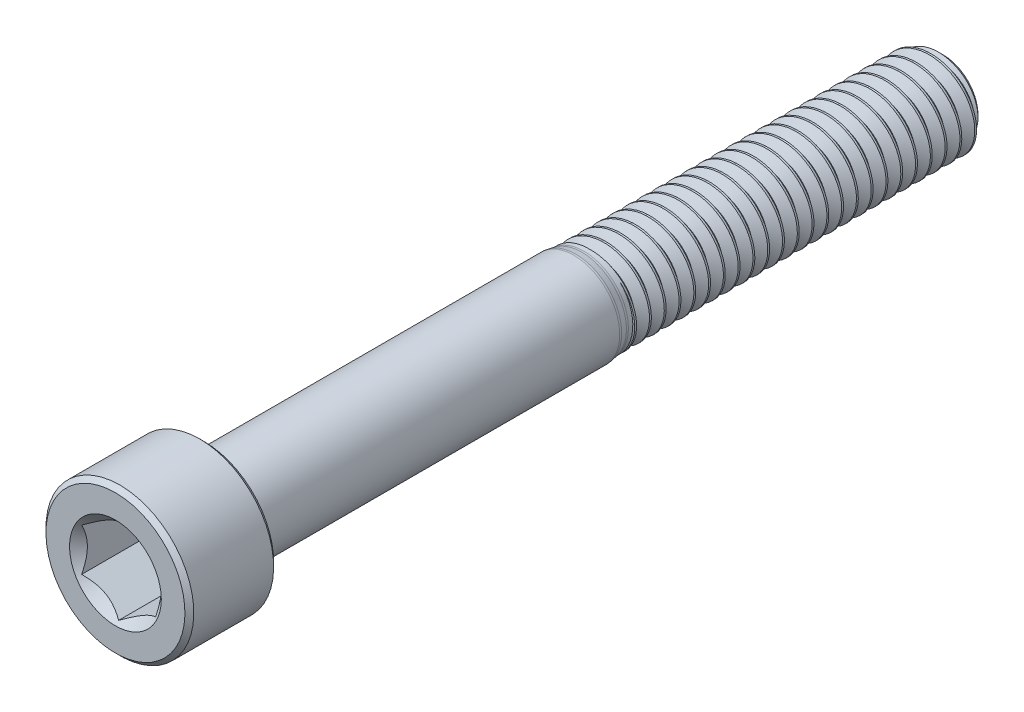
SolidWorks part; units mm, degrees
ref_plane "Front Plane" through (0, 0, 0) normal (0, 0, 1) x (1, 0, 0)
ref_plane "Top Plane" through (0, 0, 0) normal (0, 1, 0) x (1, 0, 0)
ref_plane "Right Plane" through (0, 0, 0) normal (1, 0, 0) x (0, 0, -1)
sketch "Sketch1" plane through (0, 0, 0) normal (1, 0, 0) x (0, 0, -1)
  line L0 (-28, 0) -> (28, 0) construction
  line L1 (28, 0) -> (28, 2.3505) construction
  line L2 (28, 2.3505) -> (27.3505, 3) construction
  line L3 (27.3505, 3) -> (27.25, 3) construction
  line L4 (27.25, 3) -> (-22, 3) construction
  line L5 (-22, 3) -> (-22, 5) construction
  line L6 (-22, 5) -> (-28, 5) construction
  line L7 (-28, 5) -> (-28, 0) construction
  line L8 (28, 2.3505) -> (28, 3) construction
  line L9 (27.9375, 3.1083) -> (28.4375, 2.2422) construction
  line L10 (28.4375, 2.2422) -> (28.9375, 3.1083) construction
  line L11 (28.9375, 3.1083) -> (27.9375, 3.1083) construction
  line L12 (28.4375, 3.1083) -> (28.4375, 3) construction
  line L13 (28.4375, 2.2422) -> (28.4375, 2.3505) construction
  line L14 (28.375, 2.3505) -> (28.5, 2.3505) construction
  line L15 (28, 3) -> (28.875, 3) construction
  line L16 (27.9688, 3.0541) -> (28.9062, 3.0541) construction
  line L17 (28, 0) -> (28, -3) construction
  line L18 (-22.3, 5) -> (-22, 4.7) construction
  line L19 (-27.7, 5) -> (-28, 4.7) construction
  line L20 (-22, 3) -> (-22, 0) construction
  line L21 (-22, 1.5) -> (-5.3333, 1.5) construction
  line L22 (-5.3333, 1.5) -> (11.3333, 1.5) construction
  line L23 (11.3333, 1.5) -> (28, 1.5) construction
  line L24 (-5.3333, 1.5) -> (-5.3333, 3) construction
  line L25 (-5.3333, 3) -> (-5.3333, 5) construction
  line L26 (11.3333, 1.5) -> (11.3333, 5) construction
  point P0 (-28, 2.5)
  point P3 (25.5, 3)
  point P4 (0, 0)
  point P18 (11.3333, 3)
  point P22 (28.4375, 2.3505)
  point P24 (27.25, 3)
  point P25 (28.4375, 3)
  point P28 (28.4375, 3.0541)
  point P29 (25.5, -3)
  point P30 (-5.3333, 3)
  point P31 (-25, 5)
  point P37 (-23.05, 5)
  point P38 (-27.55, 5)
  point P45 (-5.3333, 1.5)
  point P46 (11.3333, 1.5)
  point P49 (4, 3)
  dimension "D1" = 45
  dimension "D2" = 0.125
  dimension "D7" = 0.3
  dimension "D8" = 0.3
  dimension "D9" = 0.3
  dimension "D10" = 0.15
  dimension "D11" = 0.75
  dimension "Drive Size" = 5
  dimension "Head Diameter" = 10
  dimension "Head Height" = 6
  dimension "Thread Pitch" = 1
  dimension "Thread Dia" = 6
  dimension "Length" = 50
  dimension "D12" = 0.75
  dimension "D4" = 2.5
  dimension "Minimum Thread Length" = 24
  dimension "D3" = 26
sketch "Sketch2" plane through (0, 0, 0) normal (1, 0, 0) x (0, 0, -1)
  line L0 (-28, 0) -> (-28, 4.7)
  line L1 (-27.7, 5) -> (-22.3, 5)
  line L2 (-22, 4.7) -> (-22, 3.4083)
  line L4 (27.3505, 3) -> (28, 2.3505)
  line L5 (28, 2.3505) -> (28, 0)
  line L6 (-22, 5) -> (-28, 5) construction
  line L7 (28, 0) -> (-28, 0)
  line L8 (-27.7, 5) -> (-28, 4.7) construction
  line L10 (-27.7, 5) -> (-28, 4.7)
  line L14 (-22.3, 5) -> (-22, 4.7) construction
  line L16 (-22.3, 5) -> (-22, 4.7)
  line L17 (-22, 3) -> (-22, 5) construction
  line L18 (-21.7, 3.1083) -> (3.0069, 3.1083)
  line L19 (3.6989, 3) -> (27.3505, 3)
  line L20 (27.25, 3) -> (-22, 3) construction
  line L21 (3.1532, 3.0938) -> (3.5526, 3.0144)
  line L22 (28.9375, 3.1083) -> (27.9375, 3.1083) construction
  arc A1 (-22, 3.4083) -> (-21.7, 3.1083) centre (-21.7, 3.4083) ccw
  arc A2 (3.0069, 3.1083) -> (3.1532, 3.0938) centre (3.0069, 2.3583) cw
  arc A3 (3.5526, 3.0144) -> (3.6989, 3) centre (3.6989, 3.75) ccw
  point P39 (3.625, 3)
  dimension "D3" = 0.3
  dimension "D6" = 0.75
  dimension "D4" = 11.25
  dimension "D5" = 0.375
revolve "Revolve1" add sketch "Sketch2" angle 360 about L7
sketch "Sketch3" plane through (0, 0, 28) normal (0, 0, 1) x (1, 0, 0)
  line L1 (2.5, -1.4434) -> (2.5, 1.4434)
  line L2 (2.5, 1.4434) -> (0, 2.8868)
  line L3 (0, 2.8868) -> (-2.5, 1.4434)
  line L4 (-2.5, 1.4434) -> (-2.5, -1.4434)
  line L5 (-2.5, -1.4434) -> (0, -2.8868)
  line L6 (0, -2.8868) -> (2.5, -1.4434)
  circle A0 centre (0, 0) radius 2.5 construction
  circle A1 centre (0, 0) radius 5 construction
  circle A2 centre (0, 0) radius 5 construction
  circle A3 centre (0, 0) radius 2.8868 construction
  dimension "D1" = 5.7735
extrude "Cut-Extrude1" cut sketch "Sketch3" against normal offset from surface (5 mm away) 1 up to face at (0, 4.7, 22)
sketch "Sketch4" plane through (0, 0, 28) normal (0, 0, 1) x (1, 0, 0)
  circle A0 centre (0, 0) radius 3.1033
  dimension "D1" = 6.2065
extrude "Cut-Extrude2" cut sketch "Sketch4" against normal up to vertex (3 mm away) draft 45 up to point (0, 5, 25)
sketch "Sketch11" plane through (0, 0, 0) normal (1, 0, 0) x (0, 0, -1)
  line L0 (-28, 0) -> (28, 0) construction
  line L1 (-28, 0) -> (28, 0) construction
  line L2 (-18.75, 0) -> (-18.75, 3) construction
  line L3 (27.25, 3) -> (-22, 3) construction
  line L4 (-0.2431, 0) -> (-0.2431, 3) construction
  point P2 (-18.75, 0)
  point P3 (-0.2431, 0)
  dimension "D1" = 3.25
  dimension "D2" = 3.25
sketch "Sketch6" plane through (0, 0, -28) normal (0, 0, -1) x (-1, 0, 0)
  circle A0 centre (0, 0) radius 3
curve "Helix/Spiral1" pitch 1 height 25 radius 3 centre (0, 0, -28) axis (0, 0, 1) start towards (0, 1, 0)
sketch "Sketch10" plane through (0, 0, 0) normal (1, 0, 0) x (0, 0, -1)
  line L0 (4, -3) -> (4, 3)
  line L2 (-28, 0) -> (28, 0) construction
  point P3 (4, 0)
split "Split1" trim tools "Sketch10" bodies to split 106 resulting bodies 114 115
sketch "Sketch7" plane through (0, 0, 0) normal (1, 0, 0) x (0, 0, -1)
  line L0 (27.9688, 3.0541) -> (28.9062, 3.0541)
  line L1 (28.9062, 3.0541) -> (28.5, 2.3505)
  line L2 (28.5, 2.3505) -> (28.375, 2.3505)
  line L3 (28.375, 2.3505) -> (27.9688, 3.0541)
sweep "Cut-Sweep1" cut profiles "Sketch7" path "Helix/Spiral1" align with end faces yes
sketch "Sketch8" plane through (0, 0, 0) normal (1, 0, 0) x (0, 0, -1)
  line L0 (-22, 0) -> (-22, 3)
  line L2 (-22, 3) -> (4, 3)
  line L4 (4, 3) -> (5.7321, 0)
  line L5 (5.7321, 0) -> (-22, 0)
  line L6 (27.25, 3) -> (-22, 3) construction
  line L7 (-28, 0) -> (28, 0) construction
  dimension "D1" = 60
  dimension "D2" = 24
revolve "Revolve2" add sketch "Sketch8" angle 360 about L5
equation "\"D2@Sketch1\" = \"Thread Pitch@Sketch1\" / 8"
equation "\"D4@Helix/Spiral1\" = \"Thread Pitch@Sketch1\""
equation "\"D7@Sketch1\" = \"Head Height@Sketch1\" * .05"
equation "\"D8@Sketch1\"=\"D7@Sketch1\""
equation "\"D9@Sketch1\"=\"D7@Sketch1\""
equation "\"D10@Sketch1\"=\"D7@Sketch1\"/2"
equation "\"D11@Sketch1\"=\"D10@Sketch1\"*5"
equation "\"D4@Sketch1\"=\"Thread Pitch@Sketch1\"*2.5"
equation "\"D12@Sketch1\"=\"Thread Pitch@Sketch1\"*.75"
equation "\"D3@Helix/Spiral1\"=\"Minimum Thread Length@Sketch1\"+\"Thread Pitch@Sketch1\""
equation "\"D2@Sketch8\"=\"Minimum Thread Length@Sketch1\""
equation "\"D3@Sketch2\"=\"Thread Dia@Sketch1\"*0.05"
equation "\"D5@Sketch2\"=\"D12@Sketch1\"*0.5"
equation "\"D6@Sketch2\"=\"Thread Dia@Sketch1\"*0.125"
equation "\"D1@Sketch11\"=\"D3@Sketch1\"*0.125"
equation "\"D2@Sketch11\"=\"D1@Sketch11\""
equation "\"D1@Sketch4\"=\"D1@Sketch3\"*1.075"
